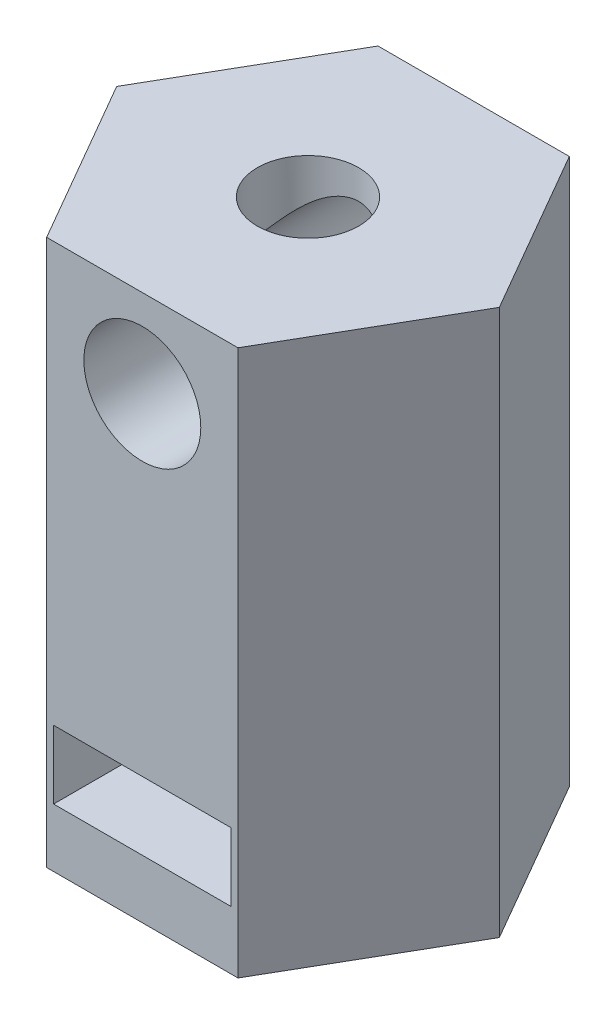
SolidWorks part; units mm, degrees
ref_plane "Front Plane" through (0, 0, 0) normal (0, 0, 1) x (1, 0, 0)
ref_plane "Top Plane" through (0, 0, 0) normal (0, 1, 0) x (1, 0, 0)
ref_plane "Right Plane" through (0, 0, 0) normal (1, 0, 0) x (0, 0, -1)
sketch "Sketch2" plane through (0, 0, 0) normal (0, 1, 0) x (1, 0, 0)
  line L1 (9.815, 0) -> (4.9075, 8.5)
  line L2 (4.9075, 8.5) -> (-4.9075, 8.5)
  line L3 (-4.9075, 8.5) -> (-9.815, 0)
  line L4 (-9.815, 0) -> (-4.9075, -8.5)
  line L5 (-4.9075, -8.5) -> (4.9075, -8.5)
  line L6 (4.9075, -8.5) -> (9.815, 0)
  circle A0 centre (0, 0) radius 8.5 construction
  circle A1 centre (0, 0) radius 2.6
  dimension "D2" = 5.2
  dimension "D1" = 17
extrude "core" add sketch "Sketch2" along normal blind 11
sketch "Sketch5" plane through (0, 0, 8.5) normal (0, 0, 1) x (1, 0, 0)
  line L0 (0, 0) -> (0, 3)
  line L1 (-4.9075, 0) -> (4.9075, 0) construction
  line L2 (4.55, 3) -> (-4.55, 3)
  line L3 (-4.55, 3) -> (4.55, 3)
  line L4 (-4.55, 3) -> (-4.55, 6.5)
  line L5 (4.55, 3) -> (4.55, 6.5)
  line L6 (-4.55, 6.5) -> (4.55, 6.5)
  point P7 (0, 3)
  dimension "D1" = 3
  dimension "D2" = 9.1
  dimension "D3" = 3.5
extrude "hex-nut" cut sketch "Sketch5" against normal blind 14.2 contours L6 L4 L2 L5 | L3 L4 L6 L5 region at (0, 4.75, 8.5)
sketch "Sketch4" plane through (0, 11, 0) normal (0, 1, 0) x (1, 0, 0)
  line L1 (9.815, 0) -> (4.9075, 8.5)
  line L2 (4.9075, 8.5) -> (-4.9075, 8.5)
  line L3 (-4.9075, 8.5) -> (-9.815, 0)
  line L4 (-9.815, 0) -> (-4.9075, -8.5)
  line L5 (-4.9075, -8.5) -> (4.9075, -8.5)
  line L6 (4.9075, -8.5) -> (9.815, 0)
  circle A0 centre (0, 0) radius 8.5 construction
  circle A1 centre (0, 0) radius 2.6
  dimension "D1" = 5.2
  dimension "D2" = 17
extrude "bolt-guard" add sketch "Sketch4" along normal blind 2 contours L1 L2 L3 L4 L5 L6
sketch "Sketch7" plane through (0, 13, 0) normal (0, 1, 0) x (1, 0, 0)
  line L1 (9.815, 0) -> (4.9075, 8.5)
  line L2 (4.9075, 8.5) -> (-4.9075, 8.5)
  line L3 (-4.9075, 8.5) -> (-9.815, 0)
  line L4 (-9.815, 0) -> (-4.9075, -8.5)
  line L5 (-4.9075, -8.5) -> (4.9075, -8.5)
  line L6 (4.9075, -8.5) -> (9.815, 0)
  circle A0 centre (0, 0) radius 2.6
  circle A1 centre (0, 0) radius 8.5 construction
  dimension "D1" = 5.2
extrude "d-shaft" add sketch "Sketch7" along normal blind 15
sketch "Sketch8" plane through (0, 0, 8.5) normal (0, 0, 1) x (1, 0, 0)
  line L0 (0, 28) -> (0, 23.5)
  line L1 (-4.9075, 28) -> (4.9075, 28) construction
  circle A0 centre (0, 23.5) radius 3
  dimension "D2" = 6
  dimension "D1" = 4.5
extrude "set-screw" cut sketch "Sketch8" against normal through all contours A0 region at (-2.0613, 21.4387, 8.5)
